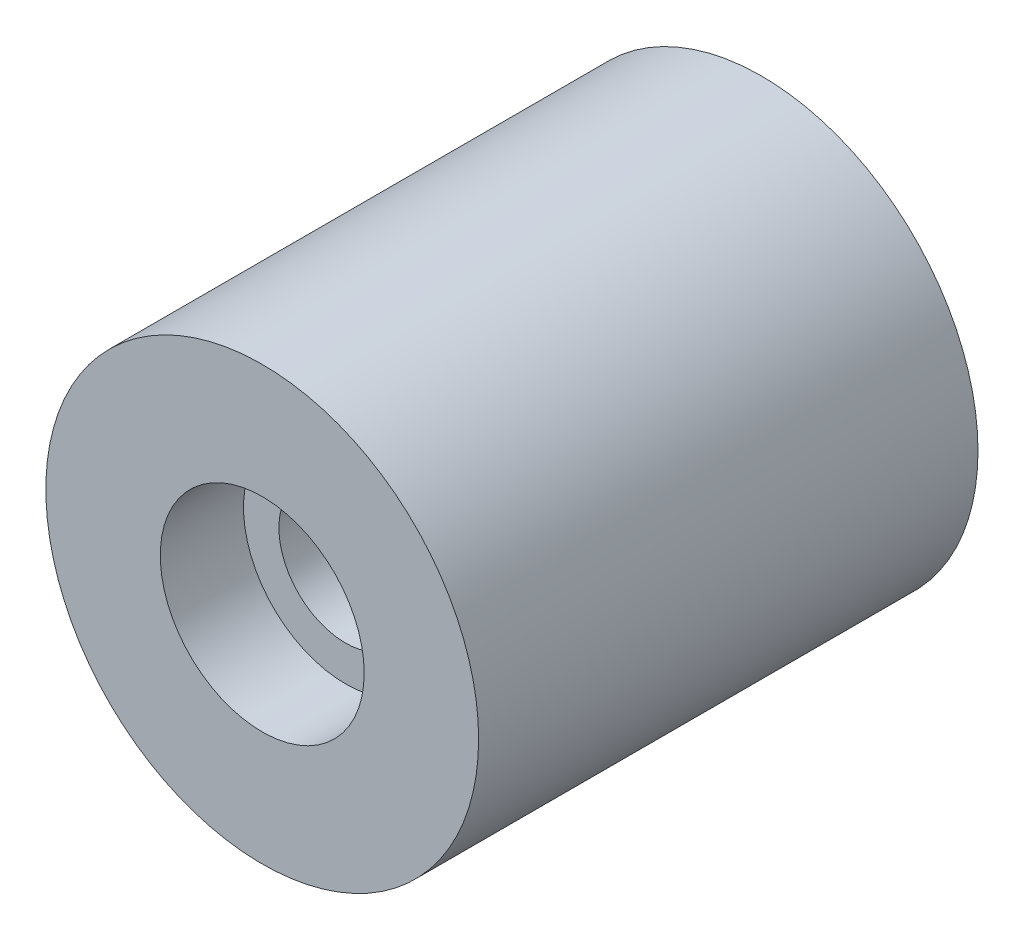
SolidWorks part; units mm, degrees
material "ABS"
ref_plane "Front Plane" through (0, 0, 0) normal (0, 0, 1) x (1, 0, 0)
ref_plane "Top Plane" through (0, 0, 0) normal (0, 1, 0) x (1, 0, 0)
ref_plane "Right Plane" through (0, 0, 0) normal (1, 0, 0) x (0, 0, -1)
ref_plane "Plane1" through (0, 0, 13.5) normal (0, 0, 1) x (1, 0, 0)
sketch "Sketch1" plane through (0, 0, 13.5) normal (0, 0, 1) x (1, 0, 0)
  circle A0 centre (15, 0) radius 2
  circle A1 centre (15, 0) radius 6.5
  dimension "D1" = 13
  dimension "D2" = 4
extrude "Boss-Extrude1" add sketch "Sketch1" along normal blind 7.5 and the other way blind 7.5
sketch "Sketch2" plane through (0, 0, 21) normal (0, 0, 1) x (1, 0, 0)
  circle A0 centre (15, 0) radius 3.0625
  dimension "D1" = 6.125
extrude "Cut-Extrude1" cut sketch "Sketch2" against normal blind 2.5
mirror "Mirror1" about plane through (0, 0, 13.5) normal (0, 0, 1) of "Cut-Extrude1"
